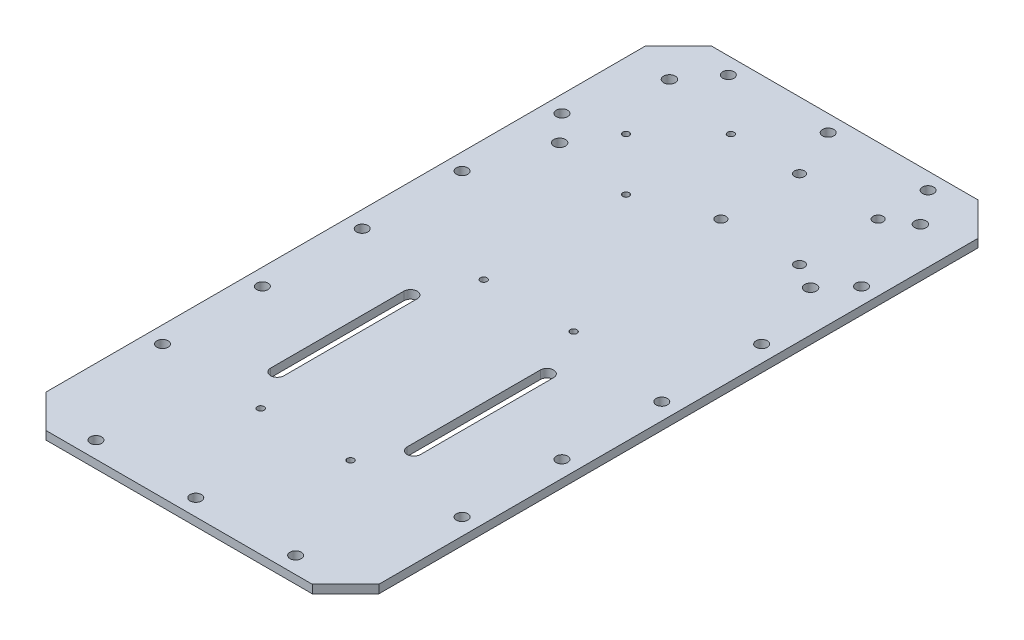
SolidWorks part; units mm, degrees
ref_plane "Front Plane" through (0, 0, 0) normal (0, 0, 1) x (1, 0, 0)
ref_plane "Top Plane" through (0, 0, 0) normal (0, 1, 0) x (1, 0, 0)
ref_plane "Right Plane" through (0, 0, 0) normal (1, 0, 0) x (0, 0, -1)
sketch "Sketch2" plane through (0, 0, 0) normal (0, 1, 0) x (1, 0, 0)
  line L0 (0, 12.7) -> (0, 241.3)
  line L1 (12.7, 254) -> (114.3, 254)
  line L2 (127, 241.3) -> (127, 12.7)
  line L3 (114.3, 0) -> (12.7, 0)
  line L4 (0, 241.3) -> (12.7, 254)
  line L5 (114.3, 254) -> (127, 241.3)
  line L6 (127, 12.7) -> (114.3, 0)
  line L7 (12.7, 0) -> (0, 12.7)
  line L8 (63.5, 254) -> (63.5, -20.3774) construction
  line L10 (0, 127) -> (136.1553, 127) construction
  line L11 (37.46, 114.3) -> (37.46, 63.5) construction
  line L15 (34.92, 114.3) -> (34.92, 63.5)
  line L16 (40, 114.3) -> (40, 63.5)
  line L32 (89.54, 114.3) -> (89.54, 63.5) construction
  line L42 (92.08, 114.3) -> (92.08, 63.5)
  line L43 (87, 114.3) -> (87, 63.5)
  circle A1 centre (6.35, 165.1) radius 2.159
  circle A13 centre (25.4, 247.65) radius 2.159
  circle A17 centre (15.621, 234.95) radius 2.2225
  circle A18 centre (15.621, 193.04) radius 2.2225
  circle A22 centre (46.355, 133.35) radius 1.27
  circle A42 centre (6.35, 203.2) radius 2.159
  circle A43 centre (63.5, 247.65) radius 2.159
  circle A46 centre (6.35, 127) radius 2.159
  arc A52 (92.08, 114.3) -> (87, 114.3) centre (89.54, 114.3) ccw
  arc A53 (87, 63.5) -> (92.08, 63.5) centre (89.54, 63.5) ccw
  arc A54 (34.92, 114.3) -> (40, 114.3) centre (37.46, 114.3) cw
  arc A55 (40, 63.5) -> (34.92, 63.5) centre (37.46, 63.5) cw
  circle A56 centre (120.65, 127) radius 2.159
  circle A57 centre (120.65, 165.1) radius 2.159
  circle A58 centre (120.65, 203.2) radius 2.159
  circle A59 centre (101.6, 247.65) radius 2.159
  circle A60 centre (101.6, 6.35) radius 2.159
  circle A61 centre (63.5, 6.35) radius 2.159
  circle A62 centre (25.4, 6.35) radius 2.159
  circle A63 centre (120.65, 50.8) radius 2.159
  circle A64 centre (6.35, 50.8) radius 2.159
  circle A65 centre (120.65, 88.9) radius 2.159
  circle A66 centre (6.35, 88.9) radius 2.159
  circle A72 centre (111.379, 193.04) radius 2.2225
  circle A73 centre (111.379, 234.95) radius 2.2225
  circle A77 centre (71.6001, 228.6) radius 1.905
  circle A78 centre (101.6, 228.6) radius 1.905
  circle A79 centre (101.6, 198.6001) radius 1.905
  circle A80 centre (71.6001, 198.6001) radius 1.905
  circle A81 centre (45.4, 228.6) radius 1.25
  circle A82 centre (45.4, 188.6) radius 1.25
  circle A83 centre (25.4, 208.6) radius 1.25
  circle A84 centre (80.645, 133.35) radius 1.27
  circle A85 centre (46.355, 48.26) radius 1.27
  circle A86 centre (80.645, 48.26) radius 1.27
  point P23 (89.54, 88.9)
  point P37 (127, 127)
  point P42 (63.5, 0)
  point P71 (37.46, 88.9)
  point P78 (0, 0)
  point P88 (0, 0)
  point P89 (0, 0)
  point P91 (0, 0)
  point P92 (0, 0)
  point P95 (0, 0)
  point P96 (0, 0)
  dimension "D8" = 95.758
  dimension "D9" = 25.4
  dimension "D10" = 50.8
  dimension "D11" = 23.5
  dimension "D13" = 34.29
  dimension "D14" = 101.6
  dimension "D16" = 12.7
  dimension "D17" = 254
  dimension "D18" = 41.91
  dimension "D20" = 29.9999
  dimension "D21" = 4.445
  dimension "D22" = 228.6
  dimension "D23" = 29.9999
  dimension "D24" = 38.1
  dimension "D25" = 3.81
  dimension "D26" = 25.4
  dimension "D27" = 40
  dimension "D28" = 20
  dimension "D29" = 3.81
  dimension "D30" = 38.1
  dimension "D31" = 3.81
  dimension "D32" = 4.318
  dimension "D33" = 4.318
  dimension "D34" = 3.81
  dimension "D35" = 20
  dimension "D36" = 101.6
  dimension "D37" = 228.6
  dimension "D38" = 2.5
  dimension "D39" = 2.5
  dimension "D40" = 2.5
  dimension "D41" = 25.4
  dimension "D42" = 25.4
  dimension "D43" = 5.08
  dimension "D44" = 4.318
  dimension "D45" = 6.35
  dimension "D46" = 63.5
  dimension "D47" = 2.54
  dimension "D48" = 85.09
  dimension "D49" = 4.318
  dimension "D50" = 4.318
  dimension "D51" = 6.35
  dimension "D55" = 2.54
  dimension "D12" = 6.35
  dimension "D7" = 127
  dimension "D15" = 12.7
  dimension "D19" = 19.05
  dimension "D52" = 34.29
  dimension "D67" = 38.1
extrude "Boss-Extrude1" add sketch "Sketch2" along normal blind 3.175 contours L7 L3 L6 L2 L5 L1 L4 L0 A46 A66 A43 A42 A53 A64 A85 A22 A72 A18 A17 A13 A59 A56 region at (63.4778, 0, -127.3675)
